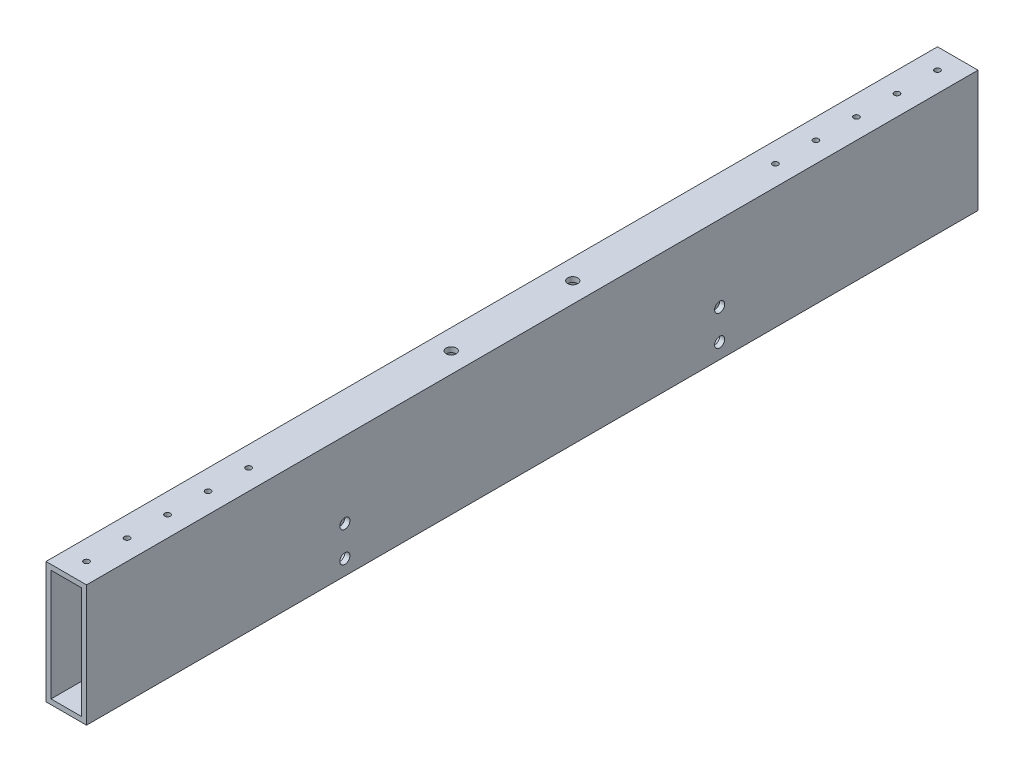
SolidWorks part; units mm, degrees
material "6061-T6 (SS)"
ref_plane "Front Plane" through (0, 0, 0) normal (0, 0, 1) x (1, 0, 0)
ref_plane "Top Plane" through (0, 0, 0) normal (0, 1, 0) x (1, 0, 0)
ref_plane "Right Plane" through (0, 0, 0) normal (1, 0, 0) x (0, 0, -1)
sketch "Sketch1" plane through (0, 0, 0) normal (0, 0, 1) x (1, 0, 0)
  line L0 (9.525, 34.925) -> (-9.525, 34.925)
  line L1 (12.7, 38.1) -> (-12.7, 38.1)
  line L2 (12.7, 38.1) -> (12.7, -38.1)
  line L3 (12.7, -38.1) -> (-12.7, -38.1)
  line L4 (-12.7, 38.1) -> (-12.7, -38.1)
  line L5 (12.7, 38.1) -> (-12.7, -38.1) construction
  line L6 (12.7, -38.1) -> (-12.7, 38.1) construction
  line L7 (-9.525, 34.925) -> (-9.525, -34.925)
  line L8 (9.525, -34.925) -> (-9.525, -34.925)
  line L9 (9.525, 34.925) -> (9.525, -34.925)
  point P0 (0, 0)
  dimension "D1" = 76.2
  dimension "D2" = 25.4
  dimension "D3" = 3.175
extrude "Boss-Extrude1" add sketch "Sketch1" along normal mid plane 558.8
sketch "Sketch2" plane through (0, 38.1, 0) normal (0, 1, 0) x (1, 0, 0)
  line L1 (12.7, 279.4) -> (-12.7, 279.4) construction
  circle A0 centre (0, 266.7) radius 1.7272
  circle A1 centre (0, 241.3) radius 1.7272
  circle A2 centre (0, 215.9) radius 1.7272
  circle A3 centre (0, 190.5) radius 1.7272
  circle A8 centre (0, 165.1) radius 1.7272
  dimension "D1" = 3.4544
  dimension "D2" = 12.7
  dimension "D3" = 5
sketch "Sketch3" plane through (0, -38.1, 0) normal (0, -1, 0) x (1, 0, 0)
  line L2 (9.525, 279.4) -> (-9.525, 279.4) construction
  circle A0 centre (0, 241.3) radius 1.7272
  circle A1 centre (0, 190.5) radius 1.7272
  circle A2 centre (0, 139.7) radius 1.7272
  circle A3 centre (0, 88.9) radius 1.7272
  circle A4 centre (0, 38.1) radius 1.7272
  circle A5 centre (0, -12.7) radius 1.7272
  circle A6 centre (0, -63.5) radius 1.7272
  circle A7 centre (0, -114.3) radius 1.7272
  circle A8 centre (0, -165.1) radius 1.7272
  circle A9 centre (0, -215.9) radius 1.7272
  circle A10 centre (0, -266.7) radius 1.7272
  point P6 (0, 279.4)
  dimension "D1" = 3.4544
  dimension "D2" = 38.1
  dimension "D4" = 50.8
  dimension "D3" = 11
extrude "Cut-Extrude2" cut sketch "Sketch3" against normal blind 6.35
hole_wizard "1/4 (0.25) Diameter Hole1" positions "Sketch9" profile "Sketch8" hole size "1/4" standard "ANSI Inch"
sketch "Sketch9" plane through (-12.7, 0, 0) normal (-1, 0, 0) x (0, 0, 1)
  line L0 (-117.475, -28.575) -> (117.475, -28.575) construction
  line L2 (279.4, -38.1) -> (-279.4, -38.1) construction
  line L4 (-127, 0) -> (127, 0) construction
  point P10 (-117.475, -28.575)
  point P11 (117.475, -28.575)
  point P25 (-117.475, -9.525)
  point P27 (117.475, -9.525)
  point P34 (0, -28.575)
  dimension "D1" = 234.95
  dimension "D2" = 9.525
  dimension "D3" = 254
  dimension "D4" = 19.05
  dimension "D5" = 19.05
sketch "Sketch8" plane through (-12.7, -28.575, -117.475) normal (0, 1, 0) x (0, 0, 1)
  line L0 (0, 0) -> (0, 27.3077)
  line L1 (0, 27.3077) -> (3.175, 25.4)
  line L2 (3.175, 25.4) -> (3.175, 0)
  line L5 (3.175, 0) -> (0, 0)
  line L10 (0, 27.3077) -> (-3.175, 25.4) construction
  line L11 (0, -6.35) -> (0, 107.95) construction
  dimension "Hole Dia." = 6.35
  dimension "Hole Depth" = 25.4
  dimension "Drill Angle" = 118
hole_wizard "1/4 (0.25) Diameter Hole2" positions "Sketch12" profile "Sketch13" hole size "1/4" standard "ANSI Inch" end condition through all
sketch "Sketch12" plane through (0, 38.1, 0) normal (0, 1, 0) x (1, 0, 0)
  line L0 (12.7, -279.4) -> (-12.7, -279.4) construction
  line L1 (0, 38.1) -> (0, -38.1) construction
  point P20 (0, -38.1)
  point P22 (0, 38.1)
  point P27 (0, -279.4)
  point P32 (0, 0)
  dimension "D7" = 76.2
sketch "Sketch13" plane through (0, 38.1, 38.1) normal (1, 0, 0) x (0, 0, 1)
  line L0 (0, 0) -> (0, 76.2)
  line L1 (0, 76.2) -> (3.175, 76.2)
  line L2 (3.175, 76.2) -> (3.175, 0)
  line L5 (3.175, 0) -> (0, 0)
  line L11 (0, -6.35) -> (0, 107.95) construction
  dimension "Thru Hole Dia." = 6.35
  dimension "Thru Hole Depth" = 76.2
extrude "Cut-Extrude4" cut sketch "Sketch2" against normal blind 6.35
mirror "Mirror1" about plane through (0, 0, 0) normal (0, 0, 1) of "Cut-Extrude4"
